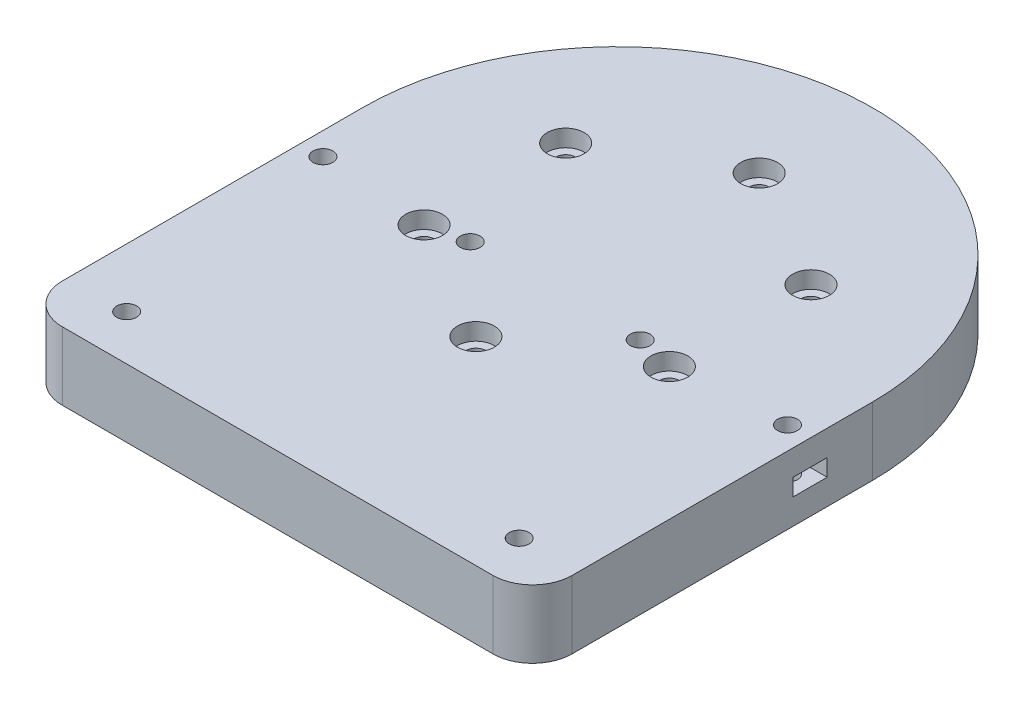
SolidWorks part; units mm, degrees
ref_plane "Front Plane" through (0, 0, 0) normal (0, 0, 1) x (1, 0, 0)
ref_plane "Top Plane" through (0, 0, 0) normal (0, 1, 0) x (1, 0, 0)
ref_plane "Right Plane" through (0, 0, 0) normal (1, 0, 0) x (0, 0, -1)
sketch "Sketch1" plane through (0, 0, 0) normal (0, 1, 0) x (1, 0, 0)
  circle A0 centre (0, 0) radius 45
  dimension "D1" = 90
extrude "Boss-Extrude1" add sketch "Sketch1" along normal blind 12
sketch "Sketch2" plane through (0, 0, 0) normal (0, -1, 0) x (1, 0, 0)
  circle A0 centre (0, 0) radius 31
  dimension "D1" = 62
extrude "Cut-Extrude1" cut sketch "Sketch2" against normal blind 6
sketch "Sketch3" plane through (0, 12, 0) normal (0, 1, 0) x (1, 0, 0)
  line L0 (0, 0) -> (0, -25) construction
  circle A0 centre (0, 0) radius 25 construction
  circle A1 centre (0, -25) radius 1.75
  circle A2 centre (-21.6506, -12.5) radius 1.75
  circle A3 centre (-21.6506, 12.5) radius 1.75
  circle A4 centre (0, 25) radius 1.75
  circle A5 centre (21.6506, 12.5) radius 1.75
  circle A6 centre (21.6506, -12.5) radius 1.75
  point P17 (0, 0)
  dimension "D1" = 50
  dimension "D2" = 3.5
  dimension "D3" = 6
extrude "Cut-Extrude2" cut sketch "Sketch3" against normal through all
sketch "Sketch4" plane through (0, 12, 0) normal (0, 1, 0) x (1, 0, 0)
  circle A0 centre (0, 25) radius 3.25
  circle A1 centre (21.6506, 12.5) radius 3.25
  circle A2 centre (21.6506, -12.5) radius 3.25
  circle A3 centre (0, -25) radius 3.25
  circle A4 centre (-21.6506, -12.5) radius 3.25
  circle A5 centre (-21.6506, 12.5) radius 3.25
  point P15 (0, 0)
  dimension "D1" = 6.5
  dimension "D2" = 6
extrude "Cut-Extrude3" cut sketch "Sketch4" against normal blind 3
sketch "Sketch5" plane through (0, 12, 0) normal (0, 1, 0) x (1, 0, 0)
  line L0 (-45, 0) -> (45, 0) construction
  line L1 (0, 0) -> (0, -45) construction
  line L2 (-45, -11) -> (45, -11) construction
  line L3 (-45, -52) -> (45, -52) construction
  line L4 (-15, -45) -> (-15, 0) construction
  line L5 (-41, -45) -> (-41, 0) construction
  line L6 (-34.64, -52) -> (-34.64, 0) construction
  line L7 (-45, 0) -> (-45, -53)
  line L8 (-38, -60) -> (38, -60)
  line L9 (45, -53) -> (45, 0)
  circle A0 centre (0, 0) radius 45 construction
  arc A1 (-45, 0) -> (45, 0) centre (0, 0) ccw
  arc A2 (38, -60) -> (45, -53) centre (38, -53) ccw
  arc A3 (-45, -53) -> (-38, -60) centre (-38, -53) ccw
  circle M14 centre (0, 0) radius 45
  dimension "D7" = 7
  dimension "D1" = 11
  dimension "D2" = 52
  dimension "D3" = 15
  dimension "D4" = 41
  dimension "D5" = 34.64
  dimension "D6" = 60
extrude "Boss-Extrude3" add sketch "Sketch5" against normal blind 12 contours L7 A3 L8 A2 L9 M14 region at (0, 12, 45.5033)
sketch "Sketch7" plane through (0, 12, 0) normal (0, 1, 0) x (1, 0, 0)
  line L0 (0, 0) -> (0, -60) construction
  line L1 (-38, -60) -> (38, -60) construction
  line L2 (-45, 0) -> (45, 0) construction
  line L3 (-45, 0) -> (-45, -53) construction
  line L4 (-45, -11) -> (45, -11) construction
  line L5 (45, -53) -> (45, 0) construction
  line L6 (-45, -52) -> (45, -52) construction
  line L7 (-41, 0) -> (-41, -60) construction
  line L8 (-15, 0) -> (-15, -60) construction
  line L9 (-34.64, 0) -> (-34.64, -60) construction
  arc A0 (45, 0) -> (-45, 0) centre (0, 0) ccw construction
  circle A1 centre (-34.64, -52) radius 1.75
  circle A2 centre (-41, -11) radius 1.75
  circle A3 centre (-15, -11) radius 1.75
  circle A4 centre (34.64, -52) radius 1.75
  circle A5 centre (15, -11) radius 1.75
  circle A6 centre (41, -11) radius 1.75
  dimension "D6" = 3.5
  dimension "D7" = 3.5
  dimension "D8" = 3.5
  dimension "D1" = 11
  dimension "D2" = 52
  dimension "D3" = 15
  dimension "D4" = 41
  dimension "D5" = 34.64
extrude "Cut-Extrude4" cut sketch "Sketch7" against normal through all
sketch "Sketch8" plane through (0, 6, 0) normal (0, -1, 0) x (1, 0, 0)
  line L0 (21.6506, 12.5) -> (15, 11) construction
  line L1 (0, 0) -> (0, 25) construction
  line L2 (15, 11) -> (13.6049, 17.1855) construction
  line L3 (14.2378, 14.3792) -> (11.6924, 12.0296)
  line L4 (11.6924, 12.0296) -> (12.4546, 8.6503)
  line L5 (12.4546, 8.6503) -> (15.7622, 7.6208)
  line L6 (15.7622, 7.6208) -> (18.3076, 9.9704)
  line L7 (18.3076, 9.9704) -> (17.5454, 13.3497)
  line L8 (17.5454, 13.3497) -> (14.2378, 14.3792)
  line L9 (-18.3076, 9.9704) -> (-17.5454, 13.3497)
  line L10 (-17.5454, 13.3497) -> (-14.2378, 14.3792)
  line L11 (-14.2378, 14.3792) -> (-11.6924, 12.0296)
  line L12 (-11.6924, 12.0296) -> (-12.4546, 8.6503)
  line L13 (-12.4546, 8.6503) -> (-15.7622, 7.6208)
  line L14 (-15.7622, 7.6208) -> (-18.3076, 9.9704)
  circle A0 centre (15, 11) radius 3 construction
  dimension "D2" = 6
  dimension "D1" = 90
extrude "Cut-Extrude5" cut sketch "Sketch8" against normal blind 3
ref_plane "Plane1" through (0, 6, 0) normal (0, -1, 0) x (-1, 0, 0)
sketch "Sketch9" plane through (0, 6, 0) normal (0, -1, 0) x (-1, 0, 0)
  line L0 (0, 0) -> (0, 31) construction
  line L1 (-41, -11) -> (41, -11) construction
  line L2 (-45, -6.0751) -> (-45, -15.3403) construction
  line L3 (-37.5359, -11) -> (-39.2679, -8)
  line L4 (-39.2679, -8) -> (-45, -8)
  line L5 (45, -14) -> (45.0012, -13.9528)
  line L6 (45, -8) -> (45, -14)
  line L7 (-45, -14) -> (-39.2679, -14)
  line L8 (-39.2679, -14) -> (-37.5359, -11)
  line L9 (-45, -53) -> (-45, 0) construction
  line L10 (-45, -8) -> (-45, -14)
  line L11 (-45, -14) -> (-45.0012, -13.9528)
  line L12 (-43.5981, -9.5) -> (-44.4641, -11) [skipped]
  line L13 (-43.5981, -12.5) -> (-42.7321, -14) [skipped]
  line L14 (39.2679, -14) -> (37.5359, -11)
  line L15 (45, -14) -> (39.2679, -14)
  line L16 (39.2679, -8) -> (45, -8)
  line L17 (37.5359, -11) -> (39.2679, -8)
  circle A0 centre (0, 0) radius 31 construction
  circle A1 centre (-41, -11) radius 3 construction
  dimension "D1" = 6
extrude "Cut-Extrude6" cut sketch "Sketch9" against normal blind 1.5 and the other way blind 1.5 contours L4 L10 L7 L8 L3 | L17 L14 L15 L6 L16 region at (41.682, 6, 11) region at (-41.682, 6, 11)
sketch "Sketch10" plane through (0, 0, 0) normal (0, -1, 0) x (1, 0, 0)
  line L0 (34.64, 52) -> (-34.64, 52) construction
  line L1 (0, 52) -> (0, 0) construction
  line L2 (31.1759, 52) -> (32.9079, 49)
  line L3 (32.9079, 49) -> (36.3721, 49)
  line L4 (36.3721, 49) -> (38.1041, 52)
  line L5 (38.1041, 52) -> (36.3721, 55)
  line L6 (36.3721, 55) -> (32.9079, 55)
  line L7 (32.9079, 55) -> (31.1759, 52)
  line L8 (-32.9079, 55) -> (-31.1759, 52)
  line L9 (-36.3721, 55) -> (-32.9079, 55)
  line L10 (-38.1041, 52) -> (-36.3721, 55)
  line L11 (-36.3721, 49) -> (-38.1041, 52)
  line L12 (-32.9079, 49) -> (-36.3721, 49)
  line L13 (-31.1759, 52) -> (-32.9079, 49)
  circle A0 centre (34.64, 52) radius 3 construction
  dimension "D1" = 6
extrude "Cut-Extrude7" cut sketch "Sketch10" against normal blind 6
